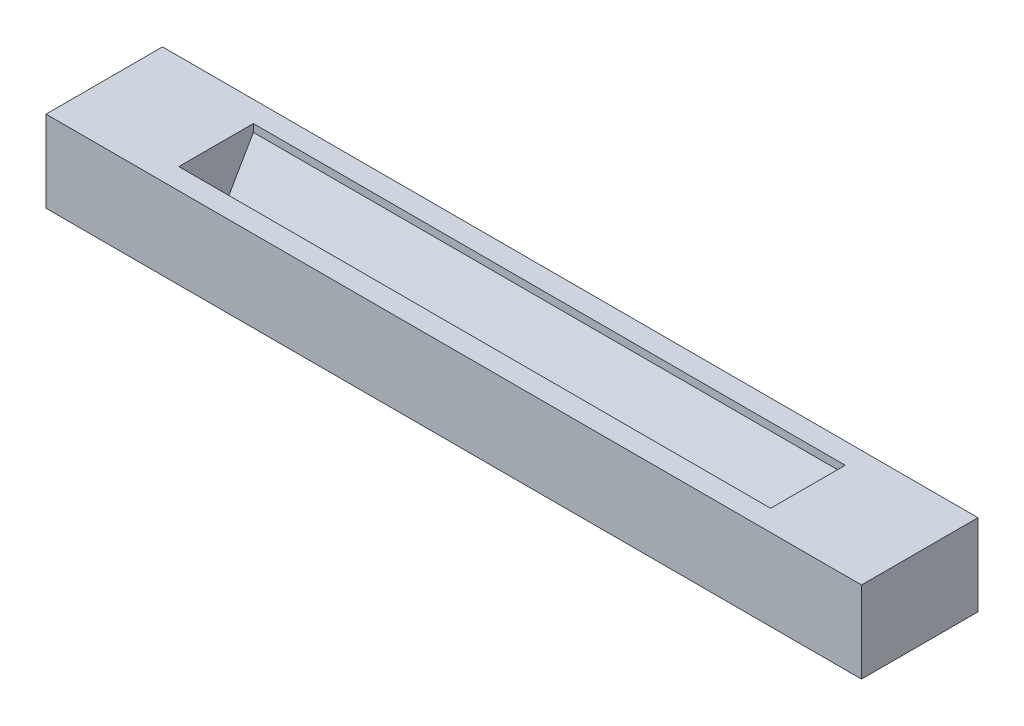
SolidWorks part; units mm, degrees
ref_plane "Top" through (0, 0, 0) normal (0, 0, 1) x (1, 0, 0)
ref_plane "Front" through (0, 0, 0) normal (0, 1, 0) x (1, 0, 0)
ref_plane "Right" through (0, 0, 0) normal (1, 0, 0) x (0, 0, -1)
sketch "Top Sketch" plane through (0, 0, 0) normal (0, 1, 0) x (1, 0, 0)
  line L2 (-35, 2) -> (-35, -3)
  line L4 (0, 2) -> (0, -3)
  line L18 (-35, 2) -> (0, 2)
  line L19 (-35, -3) -> (0, -3)
  line L28 (-35, 0) -> (0, 0) construction
  point P4 (0, 0)
  point P5 (0, 0)
  point P6 (0, 0)
  point P7 (0, 0)
  point P37 (0, -0.5)
  dimension "Width" = 5
  dimension "Length" = 35
  dimension "D3" = 0.5
extrude "Thickness Extrude" add sketch "Top Sketch" along normal blind 3.5
sketch "Handle Sketch" plane through (0, 3.5, 0) normal (0, 1, 0) x (1, 0, 0)
  line L0 (-17.5, 1.1) -> (-17.5, -2.1) construction
  line L1 (-35, -0.5) -> (0, -0.5) construction
  line L3 (-30.2, 1.1) -> (-4.8, 1.1)
  line L4 (-30.2, 1.1) -> (-30.2, -2.1)
  line L5 (-4.8, 1.1) -> (-4.8, -2.1)
  line L6 (-4.8, -2.1) -> (-30.2, -2.1)
  line L9 (-35, 2) -> (-35, -3) construction
  line L10 (0, -3) -> (0, 2) construction
  point P3 (-17.5, -0.5)
  dimension "D2" = 25.4
  dimension "D1" = 3.2
extrude "Handle Slot Cut" cut sketch "Handle Sketch" against normal blind 3.1
chamfer "Handle Slot Chamfer 1" distance 1.6 angle 60 1 edges at (-17.5, 0.4, 2.1) first distance on face at (-17.5, 0.4, 0.5)
chamfer "Handle Slot Chamfer 2" distance 1.6 angle 60 1 edges at (-17.5, 0.4, -1.1) first distance on face at (-17.5, 0.4, -0.3)
equation "\"Handle Opening Width\"= 3.2mm"
equation "\"D1@Handle Sketch\"=\"Handle Opening Width\""
equation "\"D1@Handle Slot Chamfer 1\"=\"Chamfer Base Width\""
equation "\"D1@Handle Slot Chamfer 2\"=\"Chamfer Base Width\""
equation "\"Handle Chamfer Angle\"= 60deg"
equation "\"D2@Handle Slot Chamfer 1\"=\"Handle Chamfer Angle\""
equation "\"D2@Handle Slot Chamfer 2\"=\"Handle Chamfer Angle\""
equation "\"Chamfer Base Width\"= \"Handle Opening Width\" / 2"
